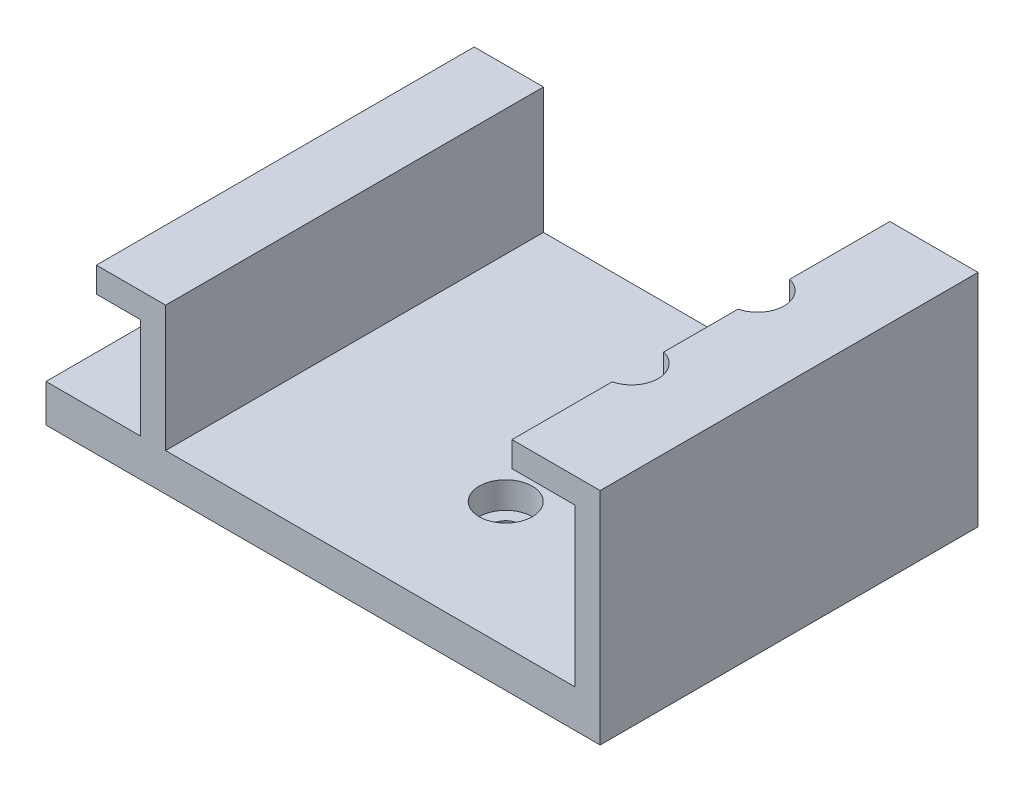
SolidWorks part; units mm, degrees
ref_plane "Front Plane" through (0, 0, 0) normal (0, 0, 1) x (1, 0, 0)
ref_plane "Top Plane" through (0, 0, 0) normal (0, 1, 0) x (1, 0, 0)
ref_plane "Right Plane" through (0, 0, 0) normal (1, 0, 0) x (0, 0, -1)
sketch "Sketch1" plane through (0, 0, 0) normal (0, 0, 1) x (1, 0, 0)
  line L0 (-14, 0) -> (0, 0)
  line L1 (0, 0) -> (0, -35)
  line L2 (0, -35) -> (-88, -35)
  line L3 (-88, -35) -> (-88, -29)
  line L4 (-88, -29) -> (-73, -29)
  line L5 (-73, -29) -> (-73, -13)
  line L6 (-73, -13) -> (-80, -13)
  line L7 (-80, -13) -> (-80, -9)
  line L8 (-80, -9) -> (-69, -9)
  line L9 (-69, -9) -> (-69, -29)
  line L10 (-69, -29) -> (-4, -29)
  line L11 (-4, -29) -> (-4, -4)
  line L12 (-4, -4) -> (-14, -4)
  line L13 (-14, -4) -> (-14, 0)
  point P7 (0, 0)
  point P16 (10.9457, -4)
  point P17 (0, 0)
  point P18 (0, 0)
  dimension "D1" = 25
  dimension "D2" = 65
  dimension "D3" = 6
  dimension "D4" = 6
  dimension "D5" = 4
  dimension "D6" = 4
  dimension "D7" = 4
  dimension "D8" = 4
  dimension "D9" = 10
  dimension "D10" = 16
  dimension "D11" = 7
  dimension "D12" = 15
extrude "Boss-Extrude1" add sketch "Sketch1" along normal blind 60
sketch "Sketch2" plane through (0, -29, 0) normal (0, 1, 0) x (1, 0, 0)
  line L0 (-15, -40) -> (-15, -20) construction
  line L1 (-15, -20) -> (-35, -20) construction
  line L2 (-35, -20) -> (-35, -40) construction
  line L3 (-35, -40) -> (-15, -40) construction
  line L4 (0, -60) -> (0, 0) construction
  line L5 (0, -30) -> (-35, -30) construction
  circle A0 centre (-15, -40) radius 2.2
  circle A1 centre (-15, -20) radius 2.2
  circle A2 centre (-35, -20) radius 2.2
  circle A3 centre (-35, -40) radius 2.2
  point P6 (-15, -30)
  point P9 (0, -30)
  dimension "D4" = 4.4
  dimension "D5" = 4.4
  dimension "D6" = 4.4
  dimension "D7" = 4.4
  dimension "D1" = 15
  dimension "D2" = 20
  dimension "D3" = 20
extrude "Cut-Extrude1" cut sketch "Sketch2" against normal blind 10
sketch "Sketch3" plane through (0, -29, 0) normal (0, 1, 0) x (1, 0, 0)
  circle A0 centre (-35, -20) radius 4.215
  circle A1 centre (-15, -20) radius 4.215
  circle A2 centre (-15, -40) radius 4.215
  circle A3 centre (-35, -40) radius 4.215
  circle A4 centre (-35, -40) radius 2.2 construction
  circle A5 centre (-15, -40) radius 2.2 construction
  circle A6 centre (-15, -20) radius 2.2 construction
  circle A7 centre (-35, -20) radius 2.2 construction
  dimension "D1" = 8.43
  dimension "D2" = 8.43
  dimension "D3" = 8.43
  dimension "D4" = 8.43
extrude "Cut-Extrude2" cut sketch "Sketch3" against normal blind 4.2 and the other way blind 40
equation "\"holeBoltDiam\"=4.4"
equation "\"D4@Sketch2\"=\"holeBoltDiam\""
equation "\"D5@Sketch2\"=\"holeBoltDiam\""
equation "\"D6@Sketch2\"=\"holeBoltDiam\""
equation "\"D7@Sketch2\"=\"holeBoltDiam\""
equation "\"insetBoltHead\"=8.43"
equation "\"D1@Sketch3\"=\"insetBoltHead\""
equation "\"D2@Sketch3\"=\"insetBoltHead\""
equation "\"D3@Sketch3\"=\"insetBoltHead\""
equation "\"D4@Sketch3\"=\"insetBoltHead\""
